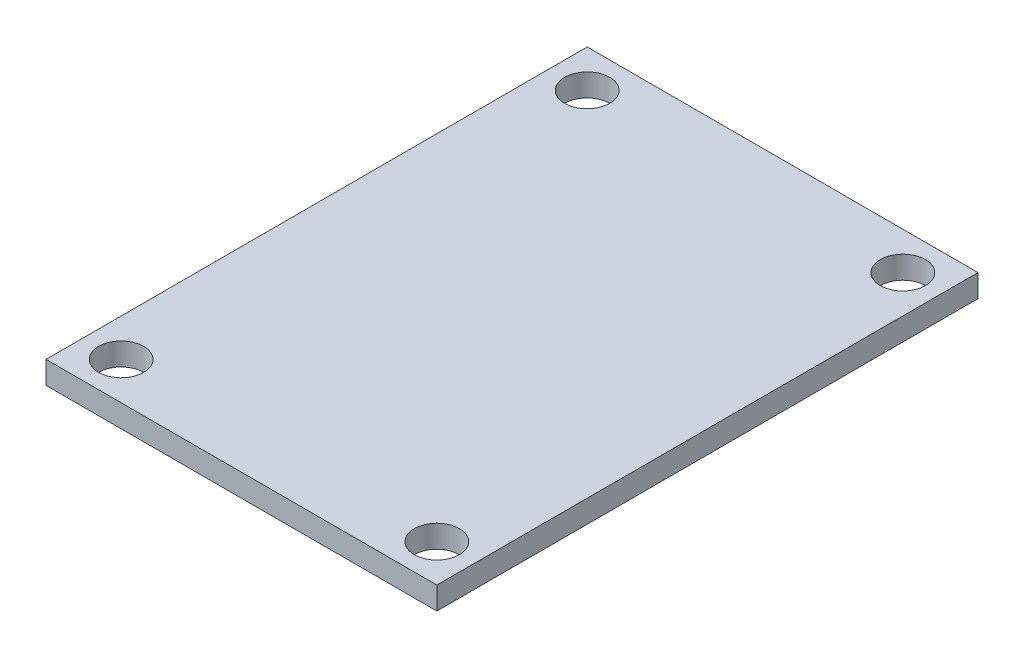
SolidWorks part; units mm, degrees
ref_plane "Ön Düzlem" through (0, 0, 0) normal (0, 0, 1) x (1, 0, 0)
ref_plane "Üst Düzlem" through (0, 0, 0) normal (0, 1, 0) x (1, 0, 0)
ref_plane "Sağ Düzlem" through (0, 0, 0) normal (1, 0, 0) x (0, 0, -1)
sketch "Sketch1" plane through (0, 0, 0) normal (0, 1, 0) x (1, 0, 0)
  line L1 (-13, 18) -> (13, 18)
  line L2 (-13, 18) -> (-13, -18)
  line L3 (-13, -18) -> (13, -18)
  line L4 (13, 18) -> (13, -18)
  line L5 (-13, 18) -> (13, -18) construction
  line L6 (-13, -18) -> (13, 18) construction
  point P0 (0, 0)
  dimension "D1" = 26
  dimension "D2" = 36
extrude "Boss-Extrude1" add sketch "Sketch1" along normal blind 1.5
sketch "Sketch2" plane through (0, 1.5, 0) normal (0, 1, 0) x (1, 0, 0)
  line L1 (-10.5, 15.5) -> (10.5, 15.5) construction
  line L2 (-10.5, 15.5) -> (-10.5, -15.5) construction
  line L3 (-10.5, -15.5) -> (10.5, -15.5) construction
  line L4 (10.5, 15.5) -> (10.5, -15.5) construction
  line L5 (-10.5, 15.5) -> (10.5, -15.5) construction
  line L6 (-10.5, -15.5) -> (10.5, 15.5) construction
  circle A0 centre (-10.5, 15.5) radius 1.5
  circle A1 centre (10.5, 15.5) radius 1.5
  circle A2 centre (10.5, -15.5) radius 1.5
  circle A3 centre (-10.5, -15.5) radius 1.5
  point P0 (0, 0)
  dimension "D3" = 3
  dimension "D4" = 3
  dimension "D5" = 3
  dimension "D6" = 3
  dimension "D1" = 31
  dimension "D2" = 21
extrude "Cut-Extrude1" cut sketch "Sketch2" against normal blind 1.5
sketch "Sketch3" plane through (0, 1.5, 0) normal (0, 1, 0) x (1, 0, 0)
  line L0 (-13, 16.5) -> (13, 16.5) construction
  line L1 (-13, 18) -> (-13, -18) construction
  line L2 (13, -18) -> (13, 18) construction
  line L3 (13, 18) -> (-13, 18) construction
  line L4 (0.02, 17.77) -> (2.52, 17.77)
  line L5 (0.02, 17.77) -> (0.02, 15.23)
  line L6 (0.02, 15.23) -> (2.52, 15.23)
  line L7 (2.52, 17.77) -> (2.52, 15.23)
  line L8 (0.02, 17.77) -> (2.52, 15.23) construction
  line L9 (0.02, 15.23) -> (2.52, 17.77) construction
  line L10 (0, 16.5) -> (0, 9.996) construction
  line L11 (-2.54, 15.23) -> (-5.08, 15.23)
  line L12 (2.54, 17.77) -> (5.08, 17.77)
  line L13 (2.54, 17.77) -> (2.54, 15.23)
  line L14 (2.54, 15.23) -> (5.08, 15.23)
  line L15 (5.08, 17.77) -> (5.08, 15.23)
  line L16 (2.54, 17.77) -> (5.08, 15.23) construction
  line L17 (2.54, 15.23) -> (5.08, 17.77) construction
  line L18 (-5.08, 17.77) -> (-5.08, 15.23)
  line L19 (-2.54, 17.77) -> (-5.08, 17.77)
  line L20 (-2.54, 17.77) -> (-2.54, 15.23)
  line L21 (-0.02, 15.23) -> (-2.52, 15.23)
  line L22 (-2.52, 17.77) -> (-2.52, 15.23)
  line L23 (-0.02, 17.77) -> (-2.52, 17.77)
  line L24 (-0.02, 17.77) -> (-0.02, 15.23)
  point P6 (1.27, 16.5)
  point P17 (3.81, 16.5)
  dimension "D1" = 2.5
  dimension "D2" = 2.54
  dimension "D3" = 1.5
  dimension "D4" = 1.27
  dimension "D5" = 2.54
  dimension "D6" = 2.54
  dimension "D7" = 2.54
extrude "Boss-Extrude2" [suppressed] add sketch "Sketch3" along normal blind 2
sketch "Sketch4" [suppressed] plane through (0, 3.5, 0) normal (0, 1, 0) x (1, 0, 0)
  line L0 (-5.08, 16.5) -> (-2.54, 16.5) construction
  line L1 (-5.08, 17.77) -> (-5.08, 15.23) construction
  line L2 (-2.54, 15.23) -> (-2.54, 17.77) construction
  line L3 (-2.54, 16.5) -> (-2.52, 16.5) construction
  line L4 (-2.52, 17.77) -> (-2.52, 15.23) construction
  line L5 (-2.52, 16.5) -> (-0.02, 16.5) construction
  line L6 (-0.02, 15.23) -> (-0.02, 17.77) construction
  line L7 (-0.02, 16.5) -> (0.02, 16.5) construction
  line L8 (0.02, 17.77) -> (0.02, 15.23) construction
  line L9 (0.02, 16.5) -> (2.52, 16.5) construction
  line L10 (2.52, 15.23) -> (2.52, 17.77) construction
  line L11 (2.52, 16.5) -> (2.54, 16.5) construction
  line L12 (2.54, 17.77) -> (2.54, 15.23) construction
  line L13 (2.54, 16.5) -> (5.08, 16.5) construction
  line L14 (5.08, 15.23) -> (5.08, 17.77) construction
  line L16 (-4.135, 16.825) -> (-3.485, 16.825)
  line L17 (-4.135, 16.825) -> (-4.135, 16.175)
  line L18 (-4.135, 16.175) -> (-3.485, 16.175)
  line L19 (-3.485, 16.825) -> (-3.485, 16.175)
  line L20 (-4.135, 16.825) -> (-3.485, 16.175) construction
  line L21 (-4.135, 16.175) -> (-3.485, 16.825) construction
  line L22 (-1.595, 16.825) -> (-0.945, 16.825)
  line L23 (-1.595, 16.825) -> (-1.595, 16.175)
  line L24 (-1.595, 16.175) -> (-0.945, 16.175)
  line L25 (-0.945, 16.825) -> (-0.945, 16.175)
  line L26 (-1.595, 16.825) -> (-0.945, 16.175) construction
  line L27 (-1.595, 16.175) -> (-0.945, 16.825) construction
  line L28 (0.945, 16.825) -> (1.595, 16.825)
  line L29 (0.945, 16.825) -> (0.945, 16.175)
  line L30 (0.945, 16.175) -> (1.595, 16.175)
  line L31 (1.595, 16.825) -> (1.595, 16.175)
  line L32 (0.945, 16.825) -> (1.595, 16.175) construction
  line L33 (0.945, 16.175) -> (1.595, 16.825) construction
  line L34 (3.485, 16.825) -> (4.135, 16.825)
  line L35 (3.485, 16.825) -> (3.485, 16.175)
  line L36 (3.485, 16.175) -> (4.135, 16.175)
  line L37 (4.135, 16.825) -> (4.135, 16.175)
  line L38 (3.485, 16.825) -> (4.135, 16.175) construction
  line L39 (3.485, 16.175) -> (4.135, 16.825) construction
  point P6 (-3.81, 16.5)
  point P29 (-1.27, 16.5)
  point P34 (1.27, 16.5)
  point P39 (3.81, 16.5)
  dimension "D1" = 0.65
  dimension "D2" = 0.65
  dimension "D3" = 0.65
  dimension "D4" = 0.65
  dimension "D5" = 0.65
  dimension "D6" = 0.65
  dimension "D7" = 0.65
  dimension "D8" = 0.65
extrude "Boss-Extrude3" [suppressed] add sketch "Sketch4" along normal blind 10 and the other way blind 5
sketch "Sketch5" plane through (0, 0, 0) normal (0, -1, 0) x (1, 0, 0)
  line L0 (-13, 18) -> (13, 18) construction
  line L1 (-7.5, 6.5) -> (7.5, 6.5)
  line L2 (-7.5, 6.5) -> (-7.5, -5)
  line L3 (-7.5, -5) -> (7.5, -5)
  line L4 (7.5, 6.5) -> (7.5, -5)
  line L5 (-7.5, 6.5) -> (7.5, -5) construction
  line L6 (-7.5, -5) -> (7.5, 6.5) construction
  point P0 (0, 0.75)
  dimension "D1" = 15
  dimension "D2" = 11.5
  dimension "D3" = 11.5
extrude "Boss-Extrude4" add sketch "Sketch5" along normal blind 2.5
sketch "Sketch6" plane through (0, 0, 0) normal (0, -1, 0) x (1, 0, 0)
  line L1 (0.162, -10.3844) -> (1.9956, -10.3844)
  line L2 (0.162, -10.3844) -> (0.162, -11.6747)
  line L3 (0.162, -11.6747) -> (1.9956, -11.6747)
  line L4 (1.9956, -10.3844) -> (1.9956, -11.6747)
  line L5 (0.162, -10.3844) -> (1.9956, -11.6747) construction
  line L6 (0.162, -11.6747) -> (1.9956, -10.3844) construction
  line L7 (2.4709, -10.3844) -> (4.4403, -10.3844)
  line L8 (2.4709, -10.3844) -> (2.4709, -11.6747)
  line L9 (2.4709, -11.6747) -> (4.4403, -11.6747)
  line L10 (4.4403, -10.3844) -> (4.4403, -11.6747)
  line L11 (2.4709, -10.3844) -> (4.4403, -11.6747) construction
  line L12 (2.4709, -11.6747) -> (4.4403, -10.3844) construction
  line L13 (4.9836, -10.3844) -> (6.6813, -10.3844)
  line L14 (4.9836, -10.3844) -> (4.9836, -11.6747)
  line L15 (4.9836, -11.6747) -> (6.6813, -11.6747)
  line L16 (6.6813, -10.3844) -> (6.6813, -11.6747)
  line L17 (4.9836, -10.3844) -> (6.6813, -11.6747) construction
  line L18 (4.9836, -11.6747) -> (6.6813, -10.3844) construction
  line L19 (7.2585, -10.3844) -> (8.8205, -10.3844)
  line L20 (7.2585, -10.3844) -> (7.2585, -11.6747)
  line L21 (7.2585, -11.6747) -> (8.8205, -11.6747)
  line L22 (8.8205, -10.3844) -> (8.8205, -11.6747)
  line L23 (7.2585, -10.3844) -> (8.8205, -11.6747) construction
  line L24 (7.2585, -11.6747) -> (8.8205, -10.3844) construction
  point P0 (1.0788, -11.0295)
  point P5 (3.4556, -11.0295)
  point P10 (5.8324, -11.0295)
  point P15 (8.0395, -11.0295)
extrude "Boss-Extrude5" add sketch "Sketch6" along normal blind 1.5
fillet "Fillet1" radius 0.5 4 edges at (0, -2.5, -5) (-7.5, -2.5, 0.75) (0, -2.5, 6.5) (7.5, -2.5, 0.75)
sketch "Sketch7" plane through (0, -2.5, 0) normal (0, -1, 0) x (1, 0, 0)
  line L0 (-4.6766, -1.8606) -> (5.1292, -1.8606) construction
  text T0 "GPS"
extrude "Cut-Extrude2" cut sketch "Sketch7" against normal blind 0.5
